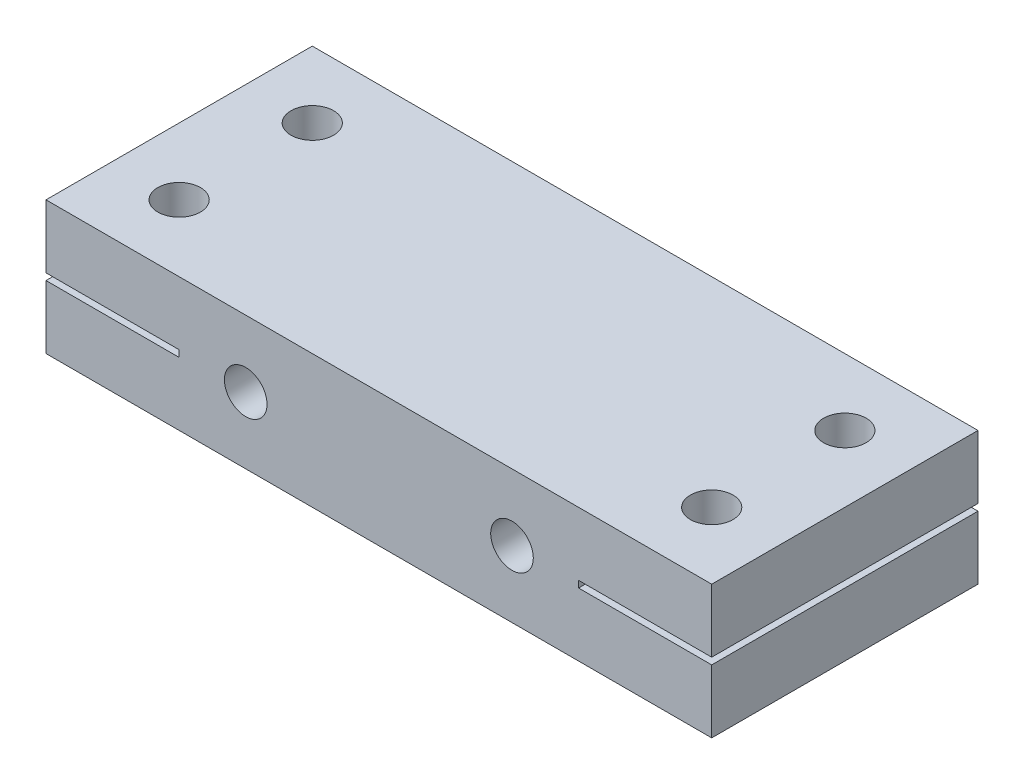
SolidWorks part; units mm, degrees
ref_plane "Front Plane" through (0, 0, 0) normal (0, 0, 1) x (1, 0, 0)
ref_plane "Top Plane" through (0, 0, 0) normal (0, 1, 0) x (1, 0, 0)
ref_plane "Right Plane" through (0, 0, 0) normal (1, 0, 0) x (0, 0, -1)
sketch "Sketch1" plane through (0, 0, 0) normal (0, 0, 1) x (1, 0, 0)
  line L0 (0, -5) -> (50, -5)
  line L1 (50, -5) -> (50, 5)
  line L2 (50, 5) -> (0, 5)
  line L3 (0, 5) -> (0, -5)
  point P6 (0, 0)
  dimension "D1" = 50
  dimension "D2" = 10
extrude "Boss-Extrude1" add sketch "Sketch1" along normal mid plane 20
sketch "Sketch2" plane through (0, 0, 10) normal (0, 0, 1) x (1, 0, 0)
  line L0 (0, 5) -> (0, -5) construction
  line L1 (0, 0.25) -> (10, 0.25)
  line L2 (0, 0.25) -> (0, -0.25)
  line L3 (0, -0.25) -> (10, -0.25)
  line L4 (10, 0.25) -> (10, -0.25)
  line L5 (50, -5) -> (50, 5) construction
  line L6 (50, 0.25) -> (40, 0.25)
  line L7 (50, 0.25) -> (50, -0.25)
  line L8 (50, -0.25) -> (40, -0.25)
  line L9 (40, 0.25) -> (40, -0.25)
  line L10 (50, 5) -> (0, 5) construction
  line L11 (0, 0.25) -> (0, -0.25)
  line L12 (50, 0.25) -> (50, -0.25)
  point P12 (10, 0)
  line M9 (0, 5) -> (0, -5)
  line M11 (50, -5) -> (50, 5)
  dimension "D2" = 0.5
  dimension "D3" = 10
extrude "Cut-Extrude1" cut sketch "Sketch2" against normal through all contours L4 L1 L3 M9 | L6 L9 L8 M11 region at (5, 0, 10) region at (45, 0, 10)
sketch "Sketch3" plane through (0, 5, 0) normal (0, 1, 0) x (1, 0, 0)
  line L0 (0, 0) -> (50, 0) construction
  line L1 (0, -10) -> (0, 10) construction
  line L2 (50, -10) -> (50, 10) construction
  line L3 (25, -10) -> (25, 10) construction
  line L4 (50, -10) -> (0, -10) construction
  line L5 (50, 10) -> (0, 10) construction
  circle A0 centre (5, 5) radius 1.6
  circle A1 centre (45, 5) radius 1.6
  circle A2 centre (5, -5) radius 1.6
  circle A3 centre (45, -5) radius 1.6
  dimension "D2" = 3.2
  dimension "D3" = 5
extrude "Cut-Extrude2" cut sketch "Sketch3" against normal through all
sketch "Sketch4" plane through (0, 0, 0) normal (0, 0, 1) x (1, 0, 0)
  line L0 (0, 5) -> (0, 0) construction
  line L2 (0, 0) -> (50, 0) construction
  line L4 (50, 0) -> (70, 0) construction
  line L5 (0, 0) -> (-20, 0) construction
  line L6 (50, 0.25) -> (50, 5) construction
  circle A0 centre (-20, 0) radius 10 construction
  circle A1 centre (70, 0) radius 10 construction
  dimension "D1" = 20
  dimension "D2" = 20
sketch "Sketch5" plane through (0, 0, 10) normal (0, 0, 1) x (1, 0, 0)
  line L0 (0, 5) -> (0, 0.25) construction
  line L1 (0, 0) -> (15, 0) construction
  line L2 (15, 0) -> (35, 0) construction
  line L3 (50, 0.25) -> (50, 5) construction
  circle A0 centre (15, 0) radius 1.6
  circle A1 centre (35, 0) radius 1.6
  dimension "D1" = 3.2
  dimension "D2" = 15
  dimension "D3" = 15
extrude "Cut-Extrude3" cut sketch "Sketch5" against normal through all
equation "\"Leg_length\"=50"
equation "\"D1@Sketch1\"=\"Leg_length\""
equation "\"Leg_width\"=10"
equation "\"D2@Sketch1\"=\"Leg_width\""
equation "\"D1@Sketch2\"=\"Leg_width\"/2"
equation "\"Leaf_Spring_Thickness\"= 0.5"
equation "\"D2@Sketch2\"=\"Leaf_Spring_Thickness\""
equation "\"Leaf_Spring_Slot_Depth\"=10"
equation "\"D3@Sketch2\"=\"Leaf_Spring_Slot_Depth\""
equation "\"D1@Sketch3\"=\"Leaf_Spring_Slot_Depth\"/2"
equation "\"Leaf_Spring_Radii\"=20"
equation "\"D2@Sketch4\"=\"Leaf_Spring_Radii\""
